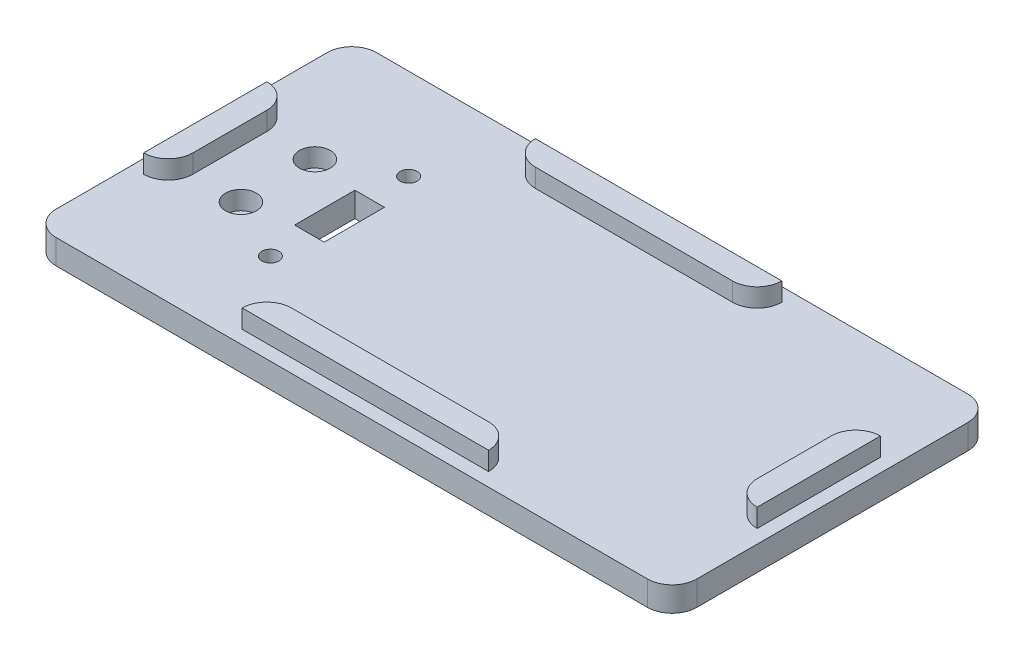
SolidWorks part; units mm, degrees
ref_plane "Front Plane" through (0, 0, 0) normal (0, 0, 1) x (1, 0, 0)
ref_plane "Top Plane" through (0, 0, 0) normal (0, 1, 0) x (1, 0, 0)
ref_plane "Right Plane" through (0, 0, 0) normal (1, 0, 0) x (0, 0, -1)
sketch "Sketch1" plane through (0, 0, 0) normal (0, 1, 0) x (1, 0, 0)
  line L1 (0, 0) -> (121.92, 0)
  line L2 (0, 0) -> (0, 66.04)
  line L3 (0, 66.04) -> (121.92, 66.04)
  line L4 (121.92, 0) -> (121.92, 66.04)
  dimension "D1" = 121.92
  dimension "D2" = 66.04
extrude "Boss-Extrude1" add sketch "Sketch1" along normal blind 5.08
fillet "Fillet1" radius 5.08 4 edges at (0, 2.54, -66.04) (121.92, 2.54, -66.04) (121.92, 2.54, 0) (0, 2.54, 0)
sketch "Sketch2" plane through (0, 5.08, 0) normal (0, 1, 0) x (1, 0, 0)
  line L0 (30.48, 39.243) -> (30.48, 26.797) construction
  line L1 (27.432, 39.243) -> (33.528, 39.243)
  line L2 (27.432, 39.243) -> (27.432, 26.797)
  line L3 (27.432, 26.797) -> (33.528, 26.797)
  line L4 (33.528, 39.243) -> (33.528, 26.797)
  line L5 (0, 60.96) -> (0, 5.08) construction
  line L6 (27.432, 33.02) -> (33.528, 33.02) construction
  circle A2 centre (30.48, 47.2694) radius 1.7526
  circle A3 centre (30.48, 18.7706) radius 1.7526
  dimension "D4" = 14.2494
  dimension "D2" = 3.5052
  dimension "D1" = 6.096
  dimension "D3" = 12.446
  dimension "D5" = 27.94
  dimension "D6" = 30.48
sketch "Sketch3" plane through (0, 5.08, 0) normal (0, 1, 0) x (1, 0, 0)
  line L0 (116.84, 66.04) -> (5.08, 66.04) construction
  line L1 (5.08, 0) -> (116.84, 0) construction
  line L2 (0, 60.96) -> (0, 5.08) construction
  circle A0 centre (17.78, 40.64) radius 3.175
  circle A1 centre (17.78, 25.4) radius 3.175
  dimension "D1" = 6.35
  dimension "D2" = 6.35
  dimension "D3" = 25.4
  dimension "D4" = 25.4
  dimension "D5" = 17.78
extrude "Cut-Extrude2" cut sketch "Sketch2" against normal up to next
extrude "Cut-Extrude3" cut sketch "Sketch3" against normal blind 3.81
sketch "Sketch4" plane through (0, 1.27, 0) normal (0, 1, 0) x (1, 0, 0)
  circle A0 centre (17.78, 40.64) radius 1.9812
  circle A1 centre (17.78, 25.4) radius 1.9812
  dimension "D1" = 3.9624
  dimension "D2" = 3.9624
extrude "Cut-Extrude4" cut sketch "Sketch4" against normal up to next
sketch "Sketch8" plane through (0, 0, 0) normal (0, -1, 0) x (1, 0, 0)
  line L0 (116.84, -66.04) -> (5.08, -66.04) construction
  line L1 (116.84, 0) -> (132.08, 0)
  line L2 (116.84, 0) -> (116.84, -66.04)
  line L3 (116.84, -66.04) -> (132.08, -66.04)
  line L4 (132.08, 0) -> (132.08, -66.04)
  dimension "D1" = 15.24
extrude "Boss-Extrude2" add sketch "Sketch8" against normal blind 5.08
fillet "Fillet4" radius 5.08 2 edges at (132.08, 2.54, 0) (132.08, 2.54, -66.04)
sketch "Sketch10" plane through (0, 5.08, 0) normal (0, 1, 0) x (1, 0, 0)
  line L0 (0, 60.96) -> (0, 5.08) construction
  line L1 (2.794, 45.72) -> (7.874, 45.72)
  line L2 (2.794, 45.72) -> (2.794, 20.32)
  line L3 (2.794, 20.32) -> (7.874, 20.32)
  line L4 (7.874, 45.72) -> (7.874, 20.32)
  line L5 (66.04, 66.04) -> (66.04, 0) construction
  line L6 (127, 66.04) -> (5.08, 66.04) construction
  line L7 (5.08, 0) -> (127, 0) construction
  line L8 (124.206, 45.72) -> (124.206, 20.32)
  line L9 (129.286, 20.32) -> (124.206, 20.32)
  line L10 (129.286, 45.72) -> (129.286, 20.32)
  line L11 (129.286, 45.72) -> (124.206, 45.72)
  dimension "D1" = 2.794
  dimension "D2" = 5.08
  dimension "D3" = 20.32
  dimension "D4" = 20.32
extrude "Boss-Extrude4" add sketch "Sketch10" along normal blind 3.81
sketch "Sketch11" plane through (0, 5.08, 0) normal (0, 1, 0) x (1, 0, 0)
  line L1 (40.64, 63.246) -> (91.44, 63.246)
  line L2 (40.64, 63.246) -> (40.64, 58.166)
  line L3 (40.64, 58.166) -> (91.44, 58.166)
  line L4 (91.44, 63.246) -> (91.44, 58.166)
  line L6 (127, 66.04) -> (5.08, 66.04) construction
  line L7 (0, 33.02) -> (132.08, 33.02) construction
  line L8 (0, 60.96) -> (0, 5.08) construction
  line L9 (132.08, 60.96) -> (132.08, 5.08) construction
  line L10 (91.44, 2.794) -> (91.44, 7.874)
  line L11 (40.64, 7.874) -> (91.44, 7.874)
  line L12 (40.64, 2.794) -> (40.64, 7.874)
  line L13 (40.64, 2.794) -> (91.44, 2.794)
  dimension "D1" = 5.08
  dimension "D2" = 50.8
  dimension "D3" = 40.64
  dimension "D4" = 2.794
extrude "Boss-Extrude5" add sketch "Sketch11" along normal blind 3.81
fillet "Fillet5" radius 5.08 8 edges at (40.64, 6.985, -7.874) (91.44, 6.985, -7.874) (124.206, 6.985, -20.32) (124.206, 6.985, -45.72) (91.44, 6.985, -58.166) (40.64, 6.985, -58.166) (7.874, 6.985, -20.32) (7.874, 6.985, -45.72)
